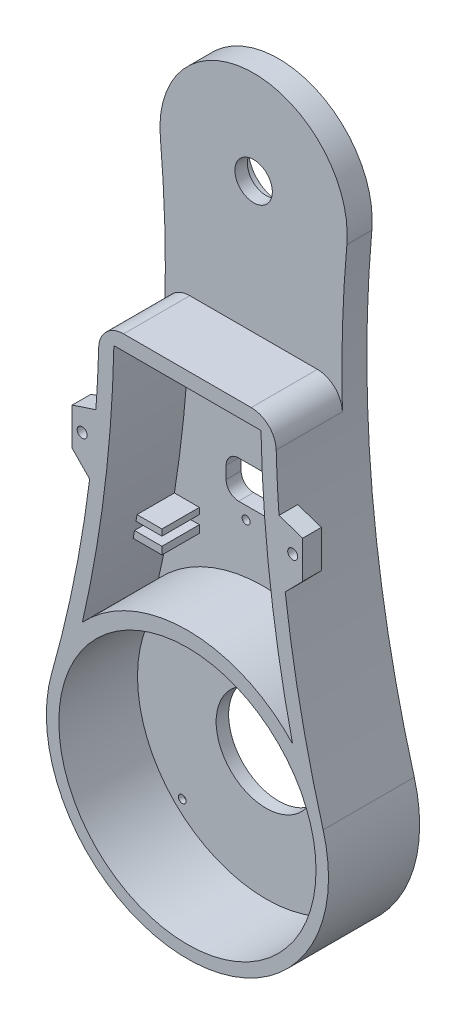
SolidWorks part; units mm, degrees
material "Custom Plastic"
ref_plane "Front Plane" through (0, 0, 0) normal (0, 0, 1) x (1, 0, 0)
ref_plane "Top Plane" through (0, 0, 0) normal (0, 1, 0) x (1, 0, 0)
ref_plane "Right Plane" through (0, 0, 0) normal (1, 0, 0) x (0, 0, -1)
sketch "Sketch1" plane through (0, 0, 0) normal (0, 0, 1) x (1, 0, 0)
  line L0 (0, 25) -> (0, 200) construction
  line L1 (-535.3493, 151.965) -> (0, 0) construction
  line L2 (-535.3493, 151.965) -> (0, 200) construction
  line L3 (0, 200) -> (0, 237.5) construction
  line L4 (0, -25) -> (0, -56.5) construction
  arc A0 (-54.3526, 15.4286) -> (54.3526, 15.4286) centre (0, 0) ccw
  arc A1 (37.35, 196.6487) -> (-37.35, 196.6487) centre (0, 200) ccw
  arc A2 (-54.3526, 15.4286) -> (-37.35, 196.6487) centre (-535.3493, 151.965) ccw
  circle A3 centre (0, 0) radius 20
  arc A4 (54.3526, 15.4286) -> (37.35, 196.6487) centre (535.3493, 151.965) cw
  circle A5 centre (0, 200) radius 7.5
  dimension "D1" = 113
  dimension "D3" = 75
  dimension "D4" = 500
  dimension "D5" = 40
  dimension "D6" = 15
  dimension "D2" = 200
extrude "Boss-Extrude1" add sketch "Sketch1" along normal blind 36.5
sketch "Sketch4" plane through (0, 0, 36.5) normal (0, 0, 1) x (1, 0, 0)
  circle A0 centre (0, 0) radius 51.5
  dimension "D1" = 103
extrude "Cut-Extrude3" cut sketch "Sketch4" against normal offset from surface (31.5 mm away) 5 up to face at (0, 97.8792, 0)
sketch "Sketch5" plane through (0, 0, 0) normal (1, 0, 0) x (0, 0, -1)
  line L0 (-10, 237.5) -> (-10, 147.5)
  line L1 (0, 237.5) -> (-36.5, 237.5) construction
  line L2 (-10, 147.5) -> (-36.5, 147.5)
  line L3 (-36.5, 196.6487) -> (-36.5, 15.4286) construction
  line L4 (0, 196.6487) -> (0, 237.5) construction
  line L5 (-36.5, 147.5) -> (-36.5, 237.5)
  line L6 (-36.5, 237.5) -> (-10, 237.5)
  dimension "D1" = 10
  dimension "D2" = 90
extrude "Cut-Extrude4" cut sketch "Sketch5" against normal through all both and the other way through all
shell "Shell1" thickness 6 removed face at (0, 63.1641, 36.5)
ref_plane "Plane1" through (0, 0, 36.5) normal (0, 0, 1) x (1, 0, 0)
sketch "Sketch7" plane through (0, 0, 36.5) normal (0, 0, 1) x (1, 0, 0)
  line L0 (-39.1592, 90.3586) -> (-46.1592, 97.5)
  line L1 (-46.1592, 97.5) -> (-46.1592, 112.5)
  line L2 (-46.1592, 112.5) -> (-36.6696, 115.6539)
  line L3 (-35.3693, 147.5) -> (35.3693, 147.5) construction
  line L4 (0, 147.5) -> (0, 57.5) construction
  line L5 (-35.3693, 147.5) -> (35.3693, 147.5) construction
  line L6 (46.1592, 97.5) -> (46.1592, 112.5)
  line L7 (39.1592, 90.3586) -> (46.1592, 97.5)
  line L8 (46.1592, 112.5) -> (36.6696, 115.6539)
  arc A0 (35.3693, 147.5) -> (54.3526, 15.4286) centre (535.3493, 151.965) ccw construction
  arc A1 (-54.3526, 15.4286) -> (-35.3693, 147.5) centre (-535.3493, 151.965) ccw construction
  arc A2 (35.3693, 147.5) -> (54.3526, 15.4286) centre (535.3493, 151.965) ccw
  arc A3 (-39.1592, 90.3586) -> (-36.6696, 115.6539) centre (-535.3493, 151.965) ccw
  circle A4 centre (-42.1592, 105) radius 2
  arc A5 (42.077, 39.189) -> (-42.077, 39.189) centre (0, 0) ccw construction
  circle A6 centre (42.1592, 105) radius 2
  arc A7 (39.1592, 90.3586) -> (36.6696, 115.6539) centre (535.3493, 151.965) cw
  point P8 (-46.1592, 105)
  dimension "D1" = 4
  dimension "D2" = 15
  dimension "D3" = 7
  dimension "D4" = 10
  dimension "D5" = 4
  dimension "D6" = 35
extrude "Boss-Extrude2" add sketch "Sketch7" against normal blind 7.5 contours A3 L2 L1 L0 | L6 L8 A7 L7 | A4 | A6
ref_plane "Plane2" through (0, 0, 6) normal (0, 0, 1) x (1, 0, 0)
sketch "Sketch8" plane through (0, 0, 6) normal (0, 0, 1) x (1, 0, 0)
  line L0 (-35.7078, 72) -> (-25.7078, 72)
  line L1 (-25.7078, 72) -> (-25.7078, 69.5)
  line L2 (-25.7078, 69.5) -> (-36.1144, 69.5)
  line L3 (-36.7051, 66) -> (-25.7078, 66)
  line L4 (-25.7078, 66) -> (-25.7078, 63)
  line L5 (-25.7078, 63) -> (-37.2316, 63)
  line L6 (-25.7078, 72) -> (-25.7078, 63) construction
  line L7 (0, 57.5) -> (0, 147.5) construction
  line L8 (-35.3693, 147.5) -> (35.3693, 147.5) construction
  line L9 (25.7078, 72) -> (25.7078, 63) construction
  line L10 (25.7078, 63) -> (37.2316, 63)
  line L11 (25.7078, 66) -> (25.7078, 63)
  line L12 (36.7051, 66) -> (25.7078, 66)
  line L13 (25.7078, 69.5) -> (36.1144, 69.5)
  line L14 (25.7078, 72) -> (25.7078, 69.5)
  line L15 (35.7078, 72) -> (25.7078, 72)
  arc A1 (-42.077, 39.189) -> (-29.4575, 141.5) centre (-535.3493, 151.965) ccw construction
  arc A2 (42.077, 39.189) -> (-42.077, 39.189) centre (0, 0) ccw construction
  arc A3 (-37.2316, 63) -> (-36.7051, 66) centre (-535.3493, 151.965) ccw
  arc A4 (42.077, 39.189) -> (-42.077, 39.189) centre (0, 0) ccw construction
  arc A5 (-36.1144, 69.5) -> (-35.7078, 72) centre (-535.3493, 151.965) ccw
  arc A6 (36.1144, 69.5) -> (35.7078, 72) centre (535.3493, 151.965) cw
  arc A7 (37.2316, 63) -> (36.7051, 66) centre (535.3493, 151.965) cw
  point P13 (0, 57.5)
  dimension "D1" = 10
  dimension "D2" = 2.5
  dimension "D3" = 12
  dimension "D4" = 3.5
  dimension "D5" = 3
extrude "Boss-Extrude3" add sketch "Sketch8" along normal blind 15
sketch "Sketch9" plane through (0, 0, 6) normal (0, 0, 1) x (1, 0, 0)
  line L0 (0, 57.5) -> (0, 192.5) construction
  line L5 (35.7078, 72) -> (25.7078, 72) construction
  line L6 (15, 97) -> (-15, 97)
  line L7 (15, 97) -> (15, 82)
  line L8 (15, 82) -> (-15, 82)
  line L9 (-15, 97) -> (-15, 82)
  line L10 (-7, 77) -> (7, 77) construction
  arc A5 (42.077, 39.189) -> (-42.077, 39.189) centre (0, 0) ccw construction
  circle A6 centre (0, 200) radius 7.5 construction
  circle A8 centre (-7, 77) radius 1.6
  circle A9 centre (7, 77) radius 1.6
  point P4 (0, 82)
  dimension "D1" = 30
  dimension "D6" = 7
  dimension "D4" = 3.2
  dimension "D5" = 3.2
  dimension "D2" = 15
  dimension "D3" = 25
  dimension "D7" = 7
  dimension "D8" = 5
extrude "Cut-Extrude5" cut sketch "Sketch9" against normal up to surface (6 mm away) and the other way through all up to face at (0, 97.8792, 0)
fillet "Fillet1" radius 10 2 edges at (35.3693, 147.5, 23.25) (-35.3693, 147.5, 23.25)
fillet "Fillet2" radius 5 4 edges at (-15, 82, 3) (-15, 97, 3) (15, 97, 3) (15, 82, 3)
sketch "Sketch10" plane through (0, 0, 5) normal (0, 0, 1) x (1, 0, 0)
  line L0 (0, 0) -> (-33.5876, 33.5876) construction
  line L1 (0, 0) -> (-82.9288, 0) construction
  circle A0 centre (0, 0) radius 47.5 construction
  circle A1 centre (-33.5876, 33.5876) radius 1.55
  circle A2 centre (33.5876, 33.5876) radius 1.55
  circle A3 centre (33.5876, -33.5876) radius 1.55
  circle A4 centre (-33.5876, -33.5876) radius 1.55
  point P5 (0, 0)
  point P6 (0, 0)
  point P8 (33.5876, 33.5876)
  point P16 (0, 0)
  dimension "D2" = 3.1
  dimension "D3" = 95
  dimension "D1" = 45
  dimension "D4" = 4
extrude "Cut-Extrude6" cut sketch "Sketch10" against normal blind 10
sketch "Sketch11" plane through (0, 0, 0) normal (0, 0, -1) x (-1, 0, 0)
  circle A0 centre (-33.5876, -33.5876) radius 1.55 construction
  circle A1 centre (33.5876, -33.5876) radius 1.55 construction
  circle A2 centre (33.5876, 33.5876) radius 1.55 construction
  circle A3 centre (-33.5876, 33.5876) radius 1.55 construction
  arc A4 (37.35, 196.6487) -> (54.3526, 15.4286) centre (535.3493, 151.965) ccw
  arc A5 (37.35, 196.6487) -> (-37.35, 196.6487) centre (0, 200) ccw
  arc A6 (-54.3526, 15.4286) -> (-37.35, 196.6487) centre (-535.3493, 151.965) ccw
  arc A7 (-54.3526, 15.4286) -> (54.3526, 15.4286) centre (0, 0) ccw
  arc A8 (37.35, 196.6487) -> (54.3526, 15.4286) centre (535.3493, 151.965) ccw
  arc A9 (37.35, 196.6487) -> (-37.35, 196.6487) centre (0, 200) ccw
  arc A10 (-54.3526, 15.4286) -> (-37.35, 196.6487) centre (-535.3493, 151.965) ccw
  arc A11 (-54.3526, 15.4286) -> (54.3526, 15.4286) centre (0, 0) ccw
  circle A12 centre (-33.5876, -33.5876) radius 1.55 construction
  circle A13 centre (33.5876, -33.5876) radius 1.55 construction
  circle A14 centre (33.5876, 33.5876) radius 1.55 construction
  circle A15 centre (-33.5876, 33.5876) radius 1.55 construction
  circle A16 centre (-33.5876, -33.5876) radius 3.55
  circle A17 centre (33.5876, -33.5876) radius 3.55
  circle A18 centre (33.5876, 33.5876) radius 3.55
  circle A19 centre (-33.5876, 33.5876) radius 3.55
  dimension "D1" = 0
  dimension "D2" = 2
extrude "Cut-Extrude8" cut sketch "Sketch11" against normal blind 3 flip side to cut
sketch "Sketch12" plane through (0, 0, 0) normal (0, 0, -1) x (-1, 0, 0)
  circle A0 centre (0, 200) radius 12.1
  dimension "D1" = 24.2
extrude "Cut-Extrude9" cut sketch "Sketch12" against normal blind 5
sketch "Sketch13" plane through (0, 0, 0) normal (0, 0, -1) x (-1, 0, 0)
  circle A0 centre (0, 200) radius 22.5 construction
  circle A1 centre (0, 222.5) radius 2.25
  circle A2 centre (22.5, 200) radius 2.25
  circle A3 centre (0, 177.5) radius 2.25
  circle A4 centre (-22.5, 200) radius 2.25
  dimension "D1" = 45
  dimension "D2" = 4.5
  dimension "D3" = 4
extrude "Cut-Extrude10" cut sketch "Sketch13" against normal blind 6
